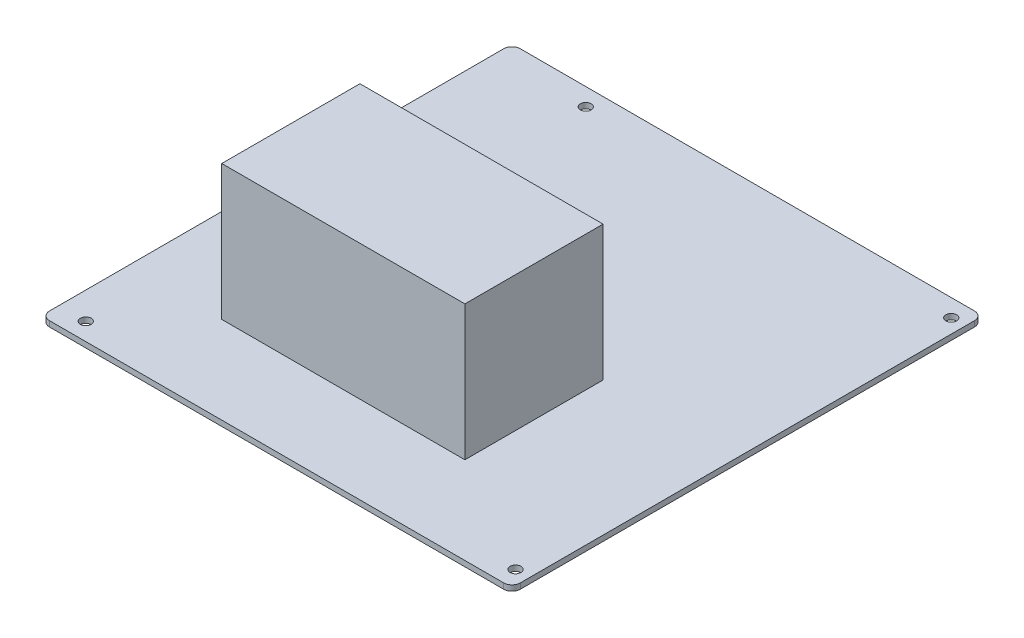
SolidWorks part; units mm, degrees
ref_plane "Front" through (0, 0, 0) normal (0, 0, 1) x (1, 0, 0)
ref_plane "Top" through (0, 0, 0) normal (0, 1, 0) x (1, 0, 0)
ref_plane "Right" through (0, 0, 0) normal (1, 0, 0) x (0, 0, -1)
sketch "Sketch1" plane through (0, 0, 0) normal (0, 1, 0) x (1, 0, 0)
  line L1 (85.09, 85.09) -> (-85.09, 85.09)
  line L2 (85.09, 85.09) -> (85.09, -85.09)
  line L3 (85.09, -85.09) -> (-85.09, -85.09)
  line L4 (-85.09, 85.09) -> (-85.09, -85.09)
  line L5 (85.09, 85.09) -> (-85.09, -85.09) construction
  line L6 (85.09, -85.09) -> (-85.09, 85.09) construction
  point P0 (0, 0)
  dimension "D1" = 170.18
  dimension "D2" = 170.18
extrude "Boss-Extrude1" add sketch "Sketch1" along normal blind 2
sketch "Sketch2" plane through (0, 2, 0) normal (0, 1, 0) x (1, 0, 0)
  line L1 (-51.3234, -3.6387) -> (36.5538, -3.6387)
  line L2 (-51.3234, -3.6387) -> (-51.3234, -53.5762)
  line L3 (-51.3234, -53.5762) -> (36.5538, -53.5762)
  line L4 (36.5538, -3.6387) -> (36.5538, -53.5762)
  line L5 (-51.3234, -3.6387) -> (36.5538, -53.5762) construction
  line L6 (-51.3234, -53.5762) -> (36.5538, -3.6387) construction
  point P0 (-7.3848, -28.6074)
  point P5 (36.5538, -53.5762)
  point P6 (-51.3234, -3.6387)
extrude "Boss-Extrude2" add sketch "Sketch2" along normal blind 48.8
fillet "Fillet1" radius 3 4 edges at (-85.09, 1, -85.09) (85.09, 1, -85.09) (85.09, 1, 85.09) (-85.09, 1, 85.09)
hole_wizard "Ø3.9 (3.9) Diameter Hole1" positions "Sketch3" profile "Sketch4" hole size "Ø3.9" standard "ANSI Metric"
sketch "Sketch3" plane through (0, 2, 0) normal (0, 1, 0) x (1, 0, 0)
  line L0 (-82.09, -85.09) -> (82.09, -85.09) construction
  line L1 (85.09, -82.09) -> (85.09, 82.09) construction
  line L3 (-52.07, 78.74) -> (80.01, 78.74) construction
  point P0 (-75.29, -78.74)
  point P2 (80.01, -78.74)
  point P4 (80.01, 78.74)
  point P6 (-52.07, 78.74)
  dimension "D1" = 6.35
  dimension "D2" = 6.35
  dimension "D3" = 5.08
  dimension "D4" = 5.08
  dimension "D5" = 157.48
  dimension "D6" = 132.08
  dimension "D7" = 155.3
sketch "Sketch4" plane through (-75.29, 2, 78.74) normal (1, 0, 0) x (0, 0, 1)
  line L0 (0, 0) -> (0, 19.9217)
  line L1 (0, 19.9217) -> (1.95, 18.75)
  line L2 (1.95, 18.75) -> (1.95, 0)
  line L5 (1.95, 0) -> (0, 0)
  line L10 (0, 19.9217) -> (-1.95, 18.75) construction
  line L11 (0, -6.35) -> (0, 107.95) construction
  dimension "Hole Dia." = 3.9
  dimension "Hole Depth" = 18.75
  dimension "Drill Angle" = 118
sketch "Sketch5" plane through (0, 2, 0) normal (0, 1, 0) x (1, 0, 0)
  line L1 (55.5339, -83.6636) -> (59.9742, -83.6636)
  line L2 (55.5339, -83.6636) -> (55.5339, -75.8548)
  line L3 (55.5339, -75.8548) -> (59.9742, -75.8548)
  line L4 (59.9742, -83.6636) -> (59.9742, -75.8548)
  line L5 (55.5339, -83.6636) -> (59.9742, -75.8548) construction
  line L6 (55.5339, -75.8548) -> (59.9742, -83.6636) construction
  point P0 (57.754, -79.7592)
extrude "Boss-Extrude3" [suppressed] add sketch "Sketch5" along normal blind 50
